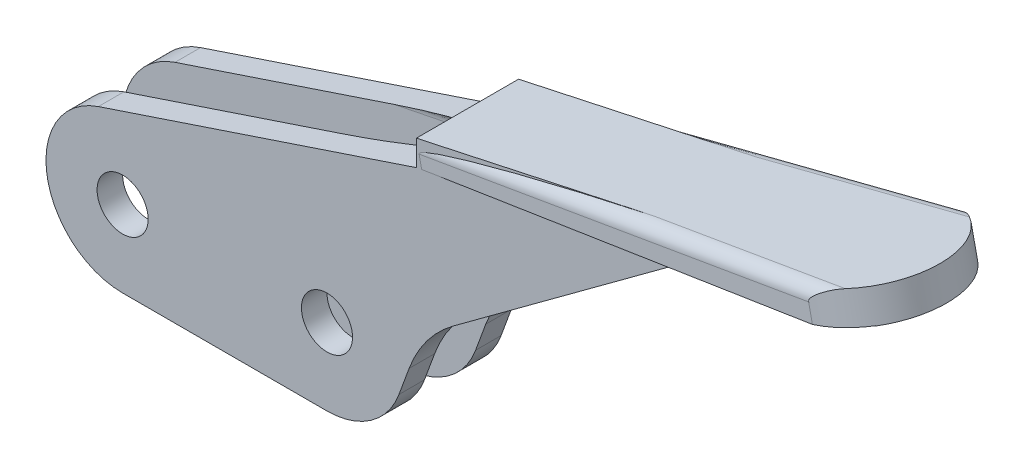
SolidWorks part; units mm, degrees
ref_plane "Plan de face" through (0, 0, 0) normal (0, 0, 1) x (1, 0, 0)
ref_plane "Plan de dessus" through (0, 0, 0) normal (0, 1, 0) x (1, 0, 0)
ref_plane "Plan de droite" through (0, 0, 0) normal (1, 0, 0) x (0, 0, -1)
sketch "Esquisse1" plane through (0, 0, 0) normal (0, 0, 1) x (1, 0, 0)
  line L0 (0, 0) -> (16, 0) construction
  line L1 (0, -6) -> (16, -6)
  line L2 (21.632, -2.0688) -> (22.4295, 0.102)
  line L3 (25.8836, 4.704) -> (43.9073, 17.9868)
  line L4 (60, 24) -> (60.5234, 21.5795)
  line L5 (60, 24) -> (23, 16)
  line L6 (23, 16) -> (23, 14)
  line L7 (23, 14) -> (-1.8992, 5.6915)
  line L8 (60.5234, 21.5795) -> (43.9073, 17.9868)
  arc A0 (-1.8992, 5.6915) -> (0, -6) centre (0, 0) ccw
  arc A1 (16, -6) -> (21.632, -2.0688) centre (16, 0) ccw
  circle A2 centre (0, 0) radius 2
  circle A3 centre (16, 0) radius 2
  arc A4 (25.8836, 4.704) -> (22.4295, 0.102) centre (31.8162, -3.3461) ccw
  dimension "D8" = 4
  dimension "D9" = 12
  dimension "D10" = 10
  dimension "D1" = 16
  dimension "D2" = 20
  dimension "D3" = 23
  dimension "D4" = 2
  dimension "D5" = 60
  dimension "D6" = 30
  dimension "D7" = 17
extrude "Boss.-Extru.1" add sketch "Esquisse1" along normal blind 2
sketch "Esquisse2" plane through (0, 0, 0) normal (0, 0, -1) x (-1, 0, 0)
  line L0 (-60.5234, 21.5795) -> (-60, 24)
  line L1 (-60, 24) -> (-23, 16)
  line L2 (-23, 16) -> (-23, 14)
  line L3 (-23, 14) -> (-60.5234, 21.5795)
extrude "Boss.-Extru.2" add sketch "Esquisse2" along normal blind 2
mirror "Symétrie1" about plane through (0, 0, -2) normal (0, 0, 1) of "Boss.-Extru.2", "Boss.-Extru.1"
sketch "Esquisse7" plane through (-2.2777, 10.5345, 0) normal (-0.2113, 0.9774, 0) x (0.9774, 0.2113, 0)
  line L0 (25.8619, -2) -> (63.6673, -3.9998)
  line L1 (63.6673, -3.9998) -> (63.7168, 2)
  line L2 (63.7168, -2) -> (63.7168, 6) construction
  line L3 (63.7168, 2) -> (63.7168, 8)
  line L4 (63.7168, 8) -> (25.8619, 6)
  line L5 (25.8619, 6) -> (25.8619, -2)
  dimension "D1" = 6
extrude "Boss.-Extru.3" add sketch "Esquisse7" against normal up to surface (2.4764 mm away) up to face at (41.7617, 17.7897, -2)
sketch "Esquisse8" plane through (-2.2777, 10.5345, 0) normal (-0.2113, 0.9774, 0) x (0.9774, 0.2113, 0)
  line L0 (25.8619, 2) -> (63.7168, 2) construction
  line L1 (25.8619, -2) -> (25.8619, 6) construction
  line L2 (63.7168, -2) -> (63.7168, 8) construction
  line L3 (57.8932, 7.8237) -> (58.1538, 10.1521)
  line L4 (58.1538, 10.1521) -> (67.0298, 10.1521)
  line L5 (67.0298, 10.1521) -> (67.3375, -6.8228)
  line L6 (67.3375, -6.8228) -> (57.2614, -6.2232)
  line L7 (57.2614, -6.2232) -> (57.8932, -3.8237)
  arc A0 (57.8932, -3.8237) -> (57.8932, 7.8237) centre (57.8932, 2) ccw
extrude "Enlèv. mat.-Extru.5" cut sketch "Esquisse8" against normal through all
fillet "Congé1" radius 1 2 edges at (41.5881, 17.7547, -4) (41.5881, 17.7547, 0)
fillet "Congé2" radius 1 2 edges at (39.1252, 19.4865, -6.8716) (39.1205, 19.4855, 2.8724)
